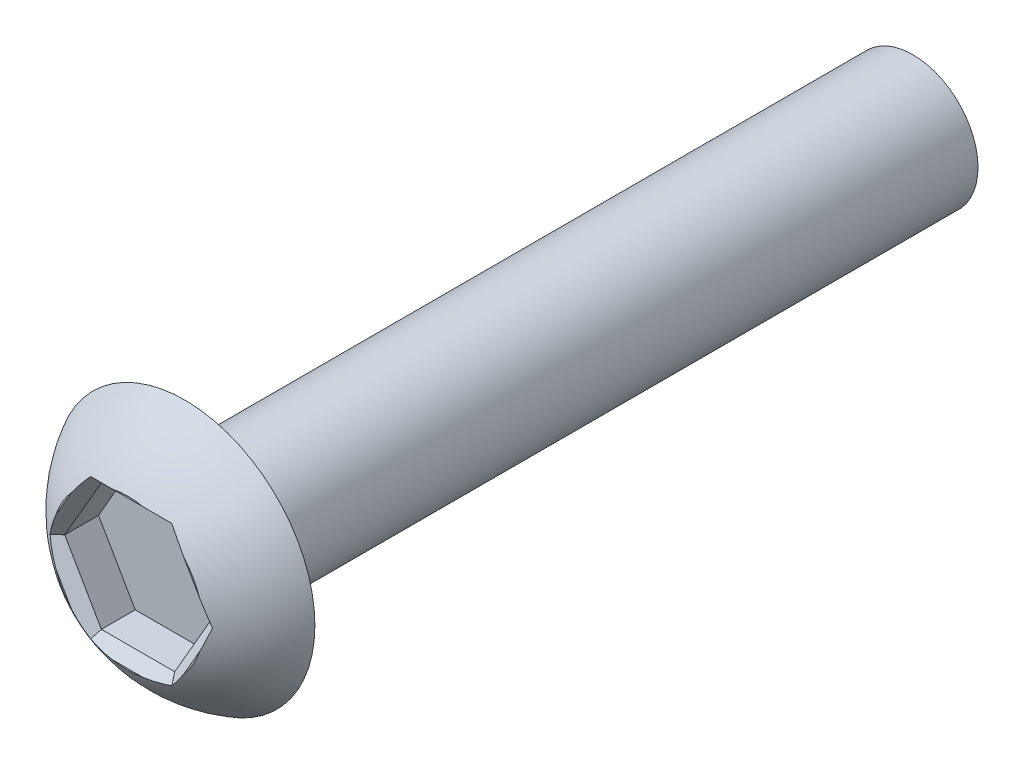
SolidWorks part; units mm, degrees
ref_plane "Front Plane" through (0, 0, 0) normal (0, 0, 1) x (1, 0, 0)
ref_plane "Top Plane" through (0, 0, 0) normal (0, 1, 0) x (1, 0, 0)
ref_plane "Right Plane" through (0, 0, 0) normal (1, 0, 0) x (0, 0, -1)
sketch "Sketch1" plane through (0, 0, 0) normal (0, 0, 1) x (1, 0, 0)
  circle A0 centre (0, 0) radius 1.25
extrude "Boss-Extrude1" add sketch "Sketch1" against normal blind 14
sketch "Sketch3" plane through (0, 0, 0) normal (1, 0, 0) x (0, 0, -1)
  line L0 (-1.5, 0) -> (-1.5, -2.0721)
  line L1 (0, 0) -> (0, 2.5)
  line L2 (-1.5, 0) -> (0, 0)
  arc A0 (-1.5, 0) -> (0, 2.5) centre (1.3333, 0) cw
  dimension "D1" = 1.5
  dimension "D2" = 2.5
revolve "Revolve1" add sketch "Sketch3" angle 360 about L2 region at (0, 0.9825, 0.6161)
sketch3d "3DSketch1" plane through (0, 0, 0) normal (0, 0, 1) x (1, 0, 0)
  dimension "D1" = 1.5
sketch "Sketch5" plane through (0, 0, 1.5) normal (0, 0, -1) x (-1, 0, 0)
  line L1 (-1.4099, 0) -> (-0.705, -1.221)
  line L2 (-0.705, -1.221) -> (0.705, -1.221)
  line L3 (0.705, -1.221) -> (1.4099, 0)
  line L4 (1.4099, 0) -> (0.705, 1.221)
  line L5 (0.705, 1.221) -> (-0.705, 1.221)
  line L6 (-0.705, 1.221) -> (-1.4099, 0)
  circle A0 centre (0, 0) radius 1.221 construction
extrude "Cut-Extrude1" cut sketch "Sketch5" along normal blind 1.25
sketch "Sketch6" plane through (0, 0, 0) normal (1, 0, 0) x (0, 0, -1)
  line L1 (-1.1, 2.3975) -> (-2.3497, 2.3975)
  line L2 (-1.1, 2.3975) -> (-1.1, -1.9866)
  line L3 (-1.1, -1.9866) -> (-2.3497, -1.9866)
  line L4 (-2.3497, 2.3975) -> (-2.3497, -1.9866)
  dimension "D1" = 1.1
extrude "Cut-Extrude2" cut sketch "Sketch6" against normal through all both and the other way through all
chamfer "Chamfer2" distance 0.2 angle 45 6 edges at (1.0574, 0.6105, 1.1) (1.0574, -0.6105, 1.1) (0, -1.221, 1.1) (-1.0574, -0.6105, 1.1) (0, 1.221, 1.1) (-1.0574, 0.6105, 1.1)
